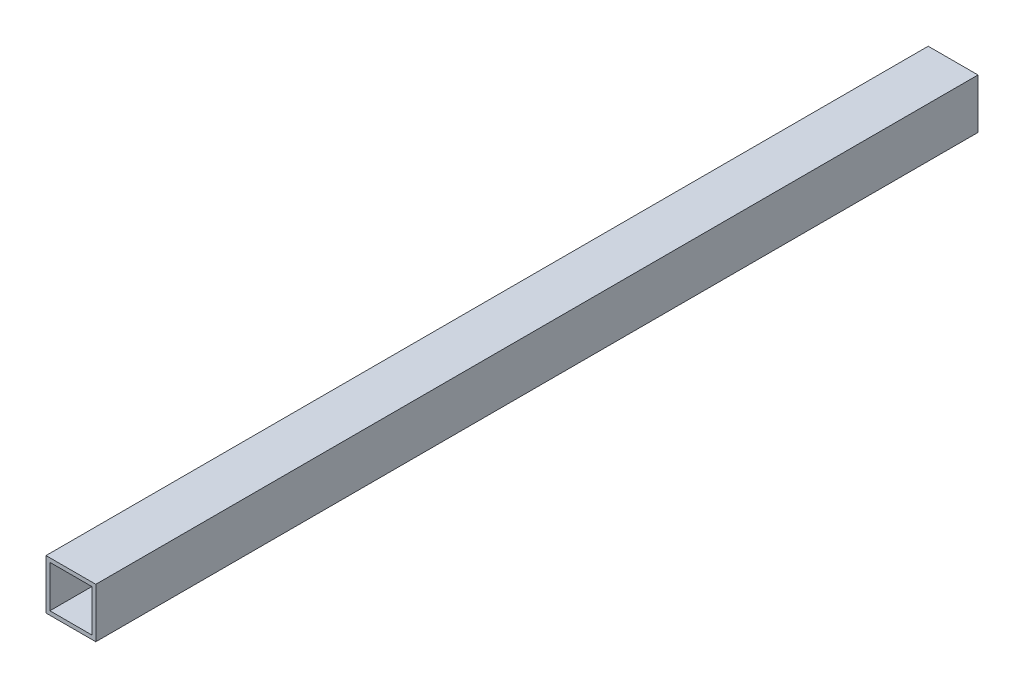
SolidWorks part; units mm, degrees
ref_plane "前基準面" through (0, 0, 0) normal (0, 0, 1) x (1, 0, 0)
ref_plane "上基準面" through (0, 0, 0) normal (0, 1, 0) x (1, 0, 0)
ref_plane "右基準面" through (0, 0, 0) normal (1, 0, 0) x (0, 0, -1)
sketch "草圖1" plane through (0, 0, 0) normal (0, 0, 1) x (1, 0, 0)
  line L0 (-10.7, 10.7) -> (10.7, 10.7)
  line L1 (-12.7, 12.7) -> (12.7, 12.7)
  line L2 (-12.7, 12.7) -> (-12.7, -12.7)
  line L3 (-12.7, -12.7) -> (12.7, -12.7)
  line L4 (12.7, 12.7) -> (12.7, -12.7)
  line L5 (-12.7, 12.7) -> (12.7, -12.7) construction
  line L6 (-12.7, -12.7) -> (12.7, 12.7) construction
  line L7 (10.7, 10.7) -> (10.7, -10.7)
  line L8 (-10.7, -10.7) -> (10.7, -10.7)
  line L9 (-10.7, 10.7) -> (-10.7, -10.7)
  point P0 (0, 0)
  dimension "D1" = 25.4
  dimension "D2" = 25.4
  dimension "D3" = 2
extrude "填料-伸長1" add sketch "草圖1" along normal blind 450 contours L1 L4 L3 L2
extrude "除料-伸長1" cut sketch "草圖1<3>" along normal through all contours L0 L7 L8 L9
sketch "草圖1<3>" plane through (0, 0, 0) normal (0, 0, 1) x (1, 0, 0) same geometry as "草圖1"
